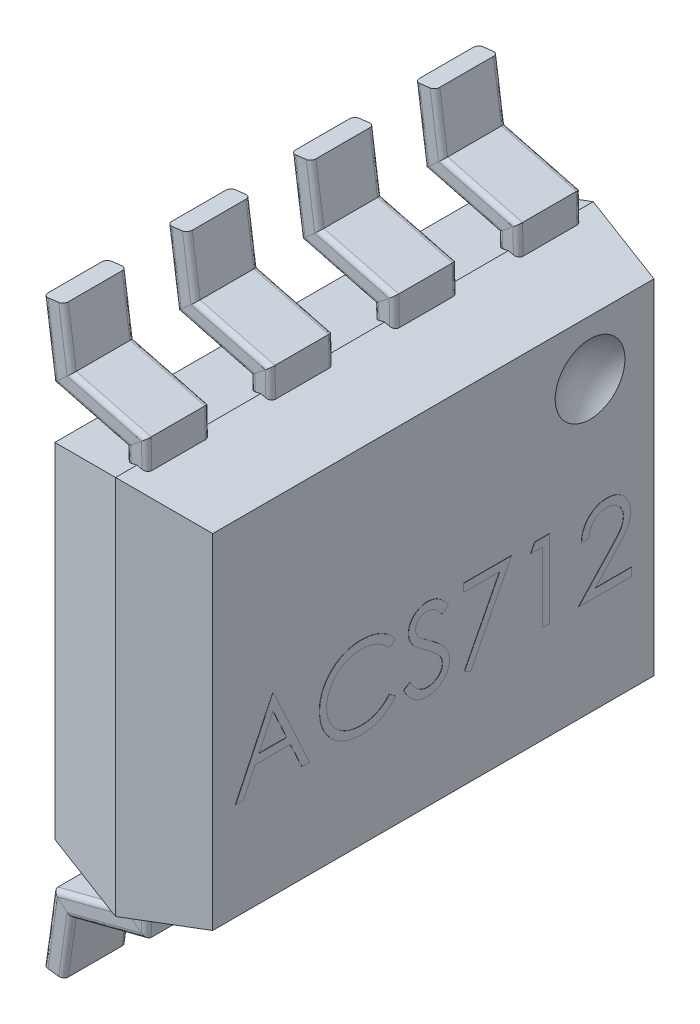
SolidWorks part; units mm, degrees
ref_plane "Front Plane" through (0, 0, 0) normal (0, 0, 1) x (1, 0, 0)
ref_plane "Top Plane" through (0, 0, 0) normal (0, 1, 0) x (1, 0, 0)
ref_plane "Right Plane" through (0, 0, 0) normal (1, 0, 0) x (0, 0, -1)
sketch "Sketch1" plane through (0, 0, 0) normal (1, 0, 0) x (0, 0, -1)
  line L0 (0, 47.1113) -> (0, -39.3384) construction
  line L1 (-62.9415, 0) -> (54.4103, 0) construction
  line L10 (2.45, -1.95) -> (-2.45, -1.95)
  line L11 (2.45, -1.95) -> (2.45, 1.95)
  line L12 (2.45, 1.95) -> (-2.45, 1.95)
  line L13 (-2.45, -1.95) -> (-2.45, 1.95)
  line L14 (2.45, -1.95) -> (-2.45, 1.95) construction
  line L15 (2.45, 1.95) -> (-2.45, -1.95) construction
  point P5 (0, 0)
  dimension "D1" = 3.9
  dimension "D2" = 4.9
extrude "Boss-Extrude1" add sketch "Sketch1" along normal mid plane 1.62 draft 13
ref_plane "Plane1" through (0, -1.763, 0) normal (0, -1, 0) x (-1, 0, 0)
sketch "Sketch2" plane through (0, -1.763, 0) normal (0, -1, 0) x (-1, 0, 0)
  line L0 (0, -2.4858) -> (0, 2.4863) construction
  line L1 (1.1137, 0) -> (-1.1296, 0) construction
  line L3 (0.055, -2.23) -> (-0.055, -2.23)
  line L4 (0.105, -2.18) -> (0.105, -1.63)
  line L5 (0.055, -1.58) -> (-0.055, -1.58)
  line L6 (-0.105, -2.18) -> (-0.105, -1.63)
  line L7 (0.105, -2.23) -> (-0.105, -1.58) construction
  line L8 (0.105, -1.58) -> (-0.105, -2.23) construction
  arc A0 (0.105, -2.18) -> (0.055, -2.23) centre (0.055, -2.18) cw
  arc A1 (-0.105, -2.18) -> (-0.055, -2.23) centre (-0.055, -2.18) ccw
  arc A2 (-0.055, -1.58) -> (-0.105, -1.63) centre (-0.055, -1.63) ccw
  arc A3 (0.105, -1.63) -> (0.055, -1.58) centre (0.055, -1.63) ccw
  point P5 (0, -1.905)
  point P10 (0, -0.635)
  dimension "D3" = 0.05
  dimension "D1" = 1.27
  dimension "D2" = 0.65
  dimension "D4" = 0.21
  dimension "D6" = 1.27
ref_plane "Plane2" through (0, 0, 1.91) normal (0, 0, 1) x (1, 0, 0)
sketch "Sketch3" plane through (0, 0, 1.91) normal (0, 0, 1) x (1, 0, 0)
  line L0 (0.008, -1.763) -> (0, -2.1479)
  line L1 (-1.1137, -1.763) -> (1.1296, -1.763) construction
  line L2 (0, -2.1479) -> (-0.7594, -2.3435)
  line L3 (-0.7594, -2.3435) -> (-0.85, -2.9879)
  line L4 (0, 0) -> (0, -3.432) construction
  line L5 (0, 1.95) -> (0, -1.95) construction
  line L7 (-0.81, 1.763) -> (-0.81, -1.763) construction
  point P14 (-0.3797, -2.2457)
  dimension "D1" = 8
  dimension "D2" = 0.84
  dimension "D3" = 0.04
  dimension "D4" = 0.385
sweep "Sweep1" add profiles "Sketch2" path "Sketch3"
pattern_linear "LPattern1" count 4 spacing 1.27 along (0, 0, 1) of "Sweep1"
mirror "Mirror1" about plane through (0, 0, 0) normal (0, 1, 0) of "LPattern1", "Sweep1"
sketch "Sketch8" plane through (0, 0, 0) normal (0, 0, 1) x (1, 0, 0)
  line L0 (-0.81, 1.763) -> (-0.81, -1.763) construction
  line L1 (0.81, 1.763) -> (0.81, -1.763) construction
  point P0 (-0.81, 0)
  point P1 (0.81, 0)
  point P4 (0, 1.95)
  point P7 (0, -1.95)
  point P9 (-0.9622, 2.9745)
  point P11 (-0.81, 1.763)
  dimension "D1" = 1.62
  dimension "D2" = 3.9
  dimension "D3" = 0.1522
sketch "Sketch10" plane through (0, 0, 0) normal (1, 0, 0) x (0, 0, -1)
  line L0 (-2.45, 1.95) -> (-2.45, -1.95) construction
  line L1 (2.45, -1.95) -> (2.45, 1.95) construction
  line L2 (-1.63, -2.9994) -> (-2.18, -2.9994) construction
  line L3 (-2.18, 2.9994) -> (-1.63, 2.9994) construction
  point P0 (-2.45, 0)
  point P1 (2.45, 0)
  point P4 (-1.905, -2.9994)
  point P7 (-1.905, 2.9994)
  point P10 (-2.23, 2.9935)
  point P13 (-1.58, 2.9935)
  dimension "D1" = 4.9
  dimension "D2" = 5.9989
  dimension "D3" = 0.65
ref_plane "Plane3" through (0, 1.2, 0) normal (0, 1, 0) x (1, 0, 0)
sketch "Sketch12" plane through (0, 1.2, 0) normal (0, 1, 0) x (1, 0, 0)
  line L0 (0.9056, 1.6077) -> (-1.0559, 1.6077) construction
  line L1 (0.81, 2.263) -> (0.81, -2.263) construction
  line L4 (0.81, 1.9655) -> (0.8578, 1.9655)
  line L5 (0.8578, 1.9655) -> (0.8578, 1.6077)
  line L6 (0.8578, 1.6077) -> (0.6618, 1.6077)
  arc A0 (0.81, 1.9655) -> (0.6618, 1.6077) centre (1.19, 1.5985) ccw
revolve "Cut-Revolve1" cut sketch "Sketch12" angle 360 about L0
sketch "Sketch14" plane through (0.81, 0, 0) normal (1, 0, 0) x (0, 0, -1)
  line L0 (-2.263, -0.763) -> (2.263, -0.763) construction
  line L1 (-2.263, 1.763) -> (-2.263, -1.763) construction
  line L2 (2.263, -1.763) -> (2.263, 1.763) construction
  line L3 (-2.263, -1.763) -> (2.263, -1.763) construction
  text T0 "ACS712" font "Century Gothic" height 0.8
  dimension "D1" = 1
extrude "Boss-Extrude2" add sketch "Sketch14" along normal blind 0.0025
